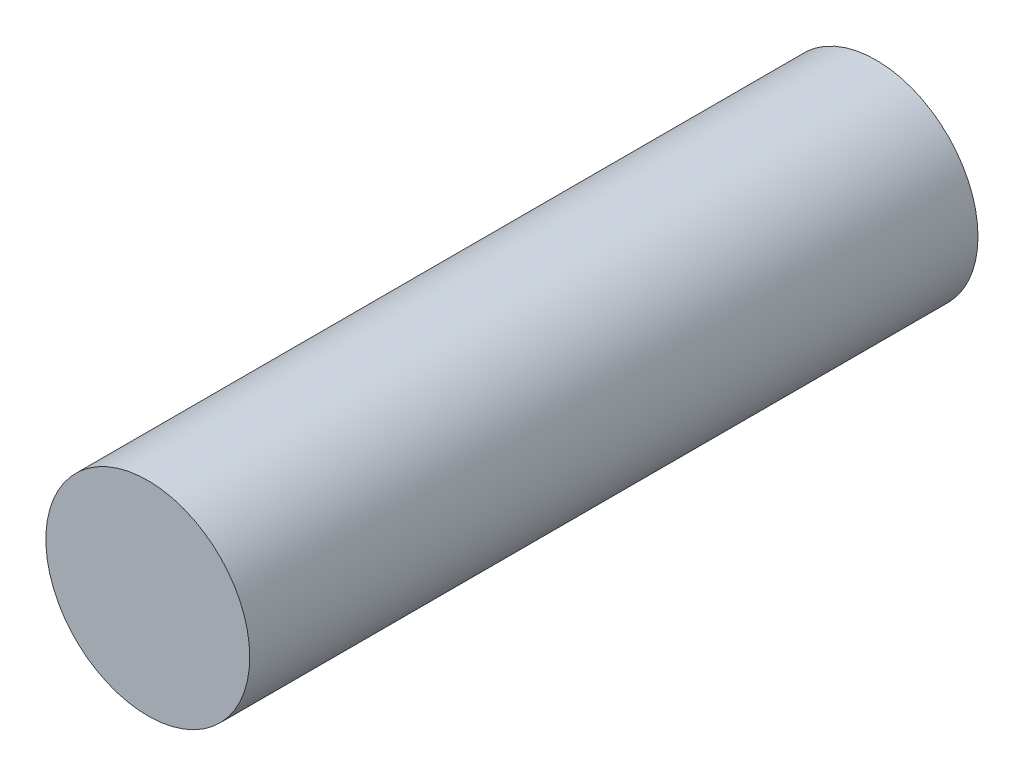
SolidWorks part; units mm, degrees
ref_plane "前视基准面" through (0, 0, 0) normal (0, 0, 1) x (1, 0, 0)
ref_plane "上视基准面" through (0, 0, 0) normal (0, 1, 0) x (1, 0, 0)
ref_plane "右视基准面" through (0, 0, 0) normal (1, 0, 0) x (0, 0, -1)
other "Configuration Table"
sketch "Sketch1" plane through (0, 0, 0) normal (0, 0, 1) x (1, 0, 0)
  circle A0 centre (0, 0) radius 35
extrude "Boss-Extrude1" add sketch "Sketch1" along normal blind 250
ref_plane "mount_face_bottom" through (0, 0, 0) normal (0, 0, 1) x (1, 0, 0)
ref_plane "mount_face_top" through (0, 0, 250) normal (0, 0, 1) x (1, 0, 0)
sketch3d "3DSketch1"
  line L0 (0, 0, 0) -> (0, 0, 250) construction
ref_axis "main_axis_z" through (0, 0, 0) along (0, 0, 1)
sketch "Sketch2" plane through (0, 0, 0) normal (0, 0, 1) x (1, 0, 0)
  circle A0 centre (0, 0) radius 35
extrude "Boss-Extrude2" add sketch "Sketch2" along normal blind 250
ref_plane "Plane3" through (0, 0, 0) normal (0, 0, 1) x (1, 0, 0)
ref_plane "Plane4" through (0, 0, 250) normal (0, 0, 1) x (1, 0, 0)
sketch3d "3DSketch2"
  line L0 (0, 0, 0) -> (0, 0, 250) construction
ref_axis "Axis2" through (0, 0, 0) along (0, 0, 1)
